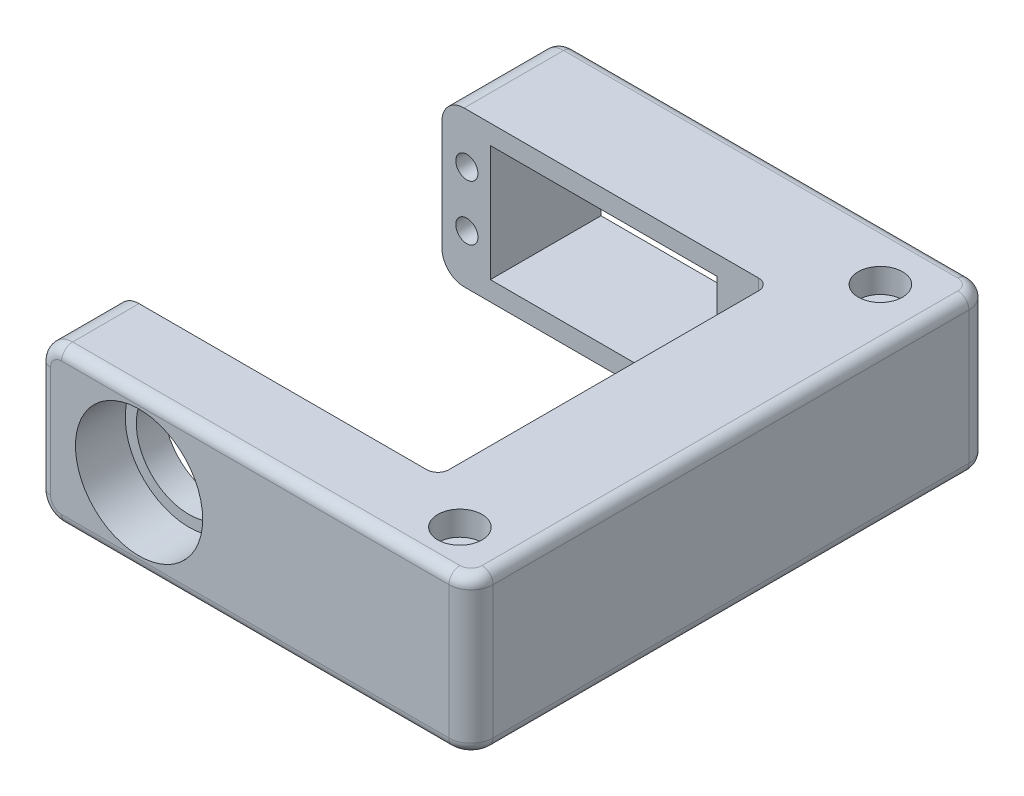
SolidWorks part; units mm, degrees
ref_plane "Top Plane" through (0, 0, 0) normal (0, 0, 1) x (1, 0, 0)
ref_plane "Right Plane" through (0, 0, 0) normal (0, 1, 0) x (1, 0, 0)
ref_plane "Front Plane" through (0, 0, 0) normal (1, 0, 0) x (0, 0, -1)
sketch "Sketch1" plane through (0, 0, 0) normal (0, 0, 1) x (1, 0, 0)
  line L0 (-10, 0) -> (30, 0) construction
  line L1 (-10, 10) -> (30, 10) construction
  line L2 (-10, 10) -> (-10, -10) construction
  line L3 (-10, -10) -> (30, -10) construction
  line L4 (30, 10) -> (30, -10) construction
  line L5 (-10, 10) -> (-17.25, 10) construction
  line L6 (-17.25, 10) -> (-17.25, -10) construction
  line L7 (-17.25, -10) -> (-10, -10) construction
  line L8 (10, 10) -> (10, -10) construction
  line L9 (37.25, -10) -> (30, -10) construction
  line L10 (37.25, 10) -> (37.25, -10) construction
  line L11 (30, 10) -> (37.25, 10) construction
  line L12 (40, 14) -> (40, -14) construction
  line L13 (-19.25, 14) -> (60, 14)
  line L14 (-19.25, 14) -> (-19.25, -14)
  line L15 (-19.25, -14) -> (60, -14)
  line L16 (60, 14) -> (60, -14)
  circle A0 centre (0, 0) radius 11 construction
  circle A1 centre (0, 0) radius 4 construction
  circle A2 centre (-14.75, 5) radius 2 construction
  circle A3 centre (-14.75, -5) radius 2 construction
  circle A4 centre (34.75, -5) radius 2 construction
  circle A5 centre (34.75, 5) radius 2 construction
  dimension "D1" = 22
  dimension "D2" = 8
  dimension "D12" = 4
  dimension "D3" = 40
  dimension "D4" = 20
  dimension "D5" = 54.5
  dimension "D6" = 37.25
  dimension "D7" = 20
  dimension "D8" = 40
  dimension "D9" = 14
  dimension "D10" = 14
  dimension "D11" = 2
  dimension "D13" = 10
  dimension "D14" = 49.5
extrude "Boss-Extrude1" add sketch "Sketch1" along normal blind 20
sketch "Sketch2" plane through (0, 0, 20) normal (0, 0, 1) x (1, 0, 0)
  line L1 (40, 14) -> (60, 14)
  line L2 (40, 14) -> (40, -14)
  line L3 (40, -14) -> (60, -14)
  line L4 (60, 14) -> (60, -14)
extrude "Boss-Extrude2" add sketch "Sketch2" along normal blind 60
sketch "Sketch3" plane through (0, 0, 80) normal (0, 0, 1) x (1, 0, 0)
  line L0 (-19.25, -14) -> (60, -14) construction
  line L1 (60, 14) -> (-18, 14)
  line L2 (60, 14) -> (60, -14)
  line L3 (60, -14) -> (-18, -14)
  line L4 (-18, 14) -> (-18, -14)
  dimension "D1" = 18
extrude "Boss-Extrude3" add sketch "Sketch3" along normal blind 14
sketch "Sketch4" plane through (0, 0, 20) normal (0, 0, 1) x (1, 0, 0)
  line L8 (-10.5, -10.5) -> (30.5, -10.5)
  line L9 (30.5, -10.5) -> (30.5, 10.5)
  line L10 (30.5, 10.5) -> (-10.5, 10.5)
  line L11 (-10.5, 10.5) -> (-10.5, -10.5)
  line L12 (-10.5, -10.5) -> (30.5, -10.5)
  line L13 (30.5, -10.5) -> (30.5, 10.5)
  line L14 (30.5, 10.5) -> (-10.5, 10.5)
  line L15 (-10.5, 10.5) -> (-10.5, -10.5)
  dimension "D1" = 0.5
extrude "Cut-Extrude1" cut sketch "Sketch4" against normal through all
sketch "Sketch5" plane through (0, 0, 20) normal (0, 0, 1) x (1, 0, 0)
  circle A0 centre (34.75, -5) radius 2 construction
  circle A1 centre (34.75, 5) radius 2 construction
  circle A2 centre (-14.75, -5) radius 2 construction
  circle A3 centre (-14.75, 5) radius 2 construction
  circle A4 centre (34.75, -5) radius 2
  circle A5 centre (34.75, 5) radius 2
  circle A6 centre (-14.75, -5) radius 2
  circle A7 centre (-14.75, 5) radius 2
extrude "Cut-Extrude2" cut sketch "Sketch5" against normal through all
sketch "Sketch6" plane through (0, 0, 0) normal (0, 0, -1) x (-1, 0, 0)
  line L0 (-10, 10.5) -> (-10, -10.5) construction
  line L1 (-34.75, 8.4641) -> (-37.75, 6.7321)
  line L2 (-37.75, 6.7321) -> (-37.75, 3.2679)
  line L3 (-37.75, 3.2679) -> (-34.75, 1.5359)
  line L4 (-34.75, 1.5359) -> (-31.75, 3.2679)
  line L5 (-31.75, 3.2679) -> (-31.75, 6.7321)
  line L6 (-31.75, 6.7321) -> (-34.75, 8.4641)
  line L7 (-34.75, -1.5359) -> (-37.75, -3.2679)
  line L8 (-37.75, -3.2679) -> (-37.75, -6.7321)
  line L9 (-37.75, -6.7321) -> (-34.75, -8.4641)
  line L10 (-34.75, -8.4641) -> (-31.75, -6.7321)
  line L11 (-31.75, -6.7321) -> (-31.75, -3.2679)
  line L12 (-31.75, -3.2679) -> (-34.75, -1.5359)
  line L13 (-30.5, 10.5) -> (10.5, 10.5) construction
  line L14 (10.5, -10.5) -> (-30.5, -10.5) construction
  line L15 (11.75, -3.2679) -> (14.75, -1.5359)
  line L16 (11.75, -6.7321) -> (11.75, -3.2679)
  line L17 (14.75, -8.4641) -> (11.75, -6.7321)
  line L18 (17.75, -6.7321) -> (14.75, -8.4641)
  line L19 (17.75, -3.2679) -> (17.75, -6.7321)
  line L20 (14.75, -1.5359) -> (17.75, -3.2679)
  line L21 (11.75, 6.7321) -> (14.75, 8.4641)
  line L22 (11.75, 3.2679) -> (11.75, 6.7321)
  line L23 (14.75, 1.5359) -> (11.75, 3.2679)
  line L24 (17.75, 3.2679) -> (14.75, 1.5359)
  line L25 (17.75, 6.7321) -> (17.75, 3.2679)
  line L26 (14.75, 8.4641) -> (17.75, 6.7321)
  circle A0 centre (-34.75, 5) radius 3 construction
  circle A1 centre (-34.75, -5) radius 3 construction
  circle A2 centre (14.75, -5) radius 3 construction
  circle A3 centre (14.75, 5) radius 3 construction
  dimension "D1" = 6
extrude "Cut-Extrude3" cut sketch "Sketch6" against normal offset from surface (14 mm away) 6 up to face at (36.75, 5, 20)
sketch "Sketch7" plane through (0, 0, 94) normal (0, 0, 1) x (1, 0, 0)
  circle A2 centre (0, 0) radius 11.5
  circle A3 centre (0, 0) radius 11.5
  dimension "D1" = 0.5
extrude "Cut-Extrude4" cut sketch "Sketch7" against normal blind 9
sketch "Sketch8" plane through (0, 0, 85) normal (0, 0, 1) x (1, 0, 0)
  circle A0 centre (0, 0) radius 9.5
  circle A1 centre (0, 0) radius 11.5 construction
  dimension "D1" = 2
extrude "Cut-Extrude5" cut sketch "Sketch8" against normal up to next
fillet "Fillet1" radius 4 4 edges at (-18, -14, 87) (-18, 14, 87) (-19.25, -14, 10) (-19.25, 14, 10)
sketch "Sketch12" plane through (0, 14, 0) normal (0, 1, 0) x (1, 0, 0)
  line L0 (60, 0) -> (-15.25, 0) construction
  line L1 (60, -94) -> (60, 0) construction
  line L2 (60, -94) -> (-14, -94) construction
  circle A0 centre (50, -10) radius 2 construction
  circle A1 centre (50, -10) radius 3.75 construction
  circle A2 centre (50, -86) radius 2 construction
  circle A3 centre (50, -86) radius 3.75 construction
  dimension "D1" = 4
  dimension "D2" = 7.5
  dimension "D5" = 8
  dimension "D3" = 10
  dimension "D4" = 10
  dimension "D6" = 10
hole_wizard "CBORE for M4 Hex Socket Head Cap Screw1" positions "Sketch13" profile "Sketch14" counterbore size "M4" standard "ISO" end condition through all
sketch "Sketch13" plane through (0, 14, 0) normal (0, 1, 0) x (1, 0, 0)
  point P2 (50, -10)
  point P7 (50, -86)
sketch "Sketch14" plane through (50, 14, 10) normal (1, 0, 0) x (0, 0, 1)
  line L0 (0, 0) -> (0, 28)
  line L1 (0, 28) -> (2.15, 28)
  line L3 (2.15, 28) -> (2.15, 4.4)
  line L4 (2.15, 4.4) -> (4, 4.4)
  line L5 (4, 4.4) -> (4, 0)
  line L7 (4, 0) -> (0, 0)
  line L11 (0, -6.35) -> (0, 107.95) construction
  dimension "Thru Hole Dia." = 4.3
  dimension "Thru Hole Depth" = 28
  dimension "C'Bore Dia." = 8
  dimension "C'Bore Depth" = 4.4
fillet "Fillet3" radius 4 2 edges at (60, 0, 0) (60, 0, 94)
fillet "Fillet4" radius 2 2 edges at (40, 0, 20) (40, 0, 80)
fillet "Fillet5" radius 2 16 edges at (58.8284, -14, 92.8284) (21, -14, 94) (-16.8284, -12.8284, 94) (-18, 0, 94) (-16.8284, 12.8284, 94) (21, 14, 94) (58.8284, 14, 92.8284) (60, 14, 47) (58.8284, 14, 1.1716) (20.375, 14, 0) (-18.0784, 12.8284, 0) (-19.25, 0, 0) (-18.0784, -12.8284, 0) (20.375, -14, 0) (58.8284, -14, 1.1716) (60, -14, 47)
